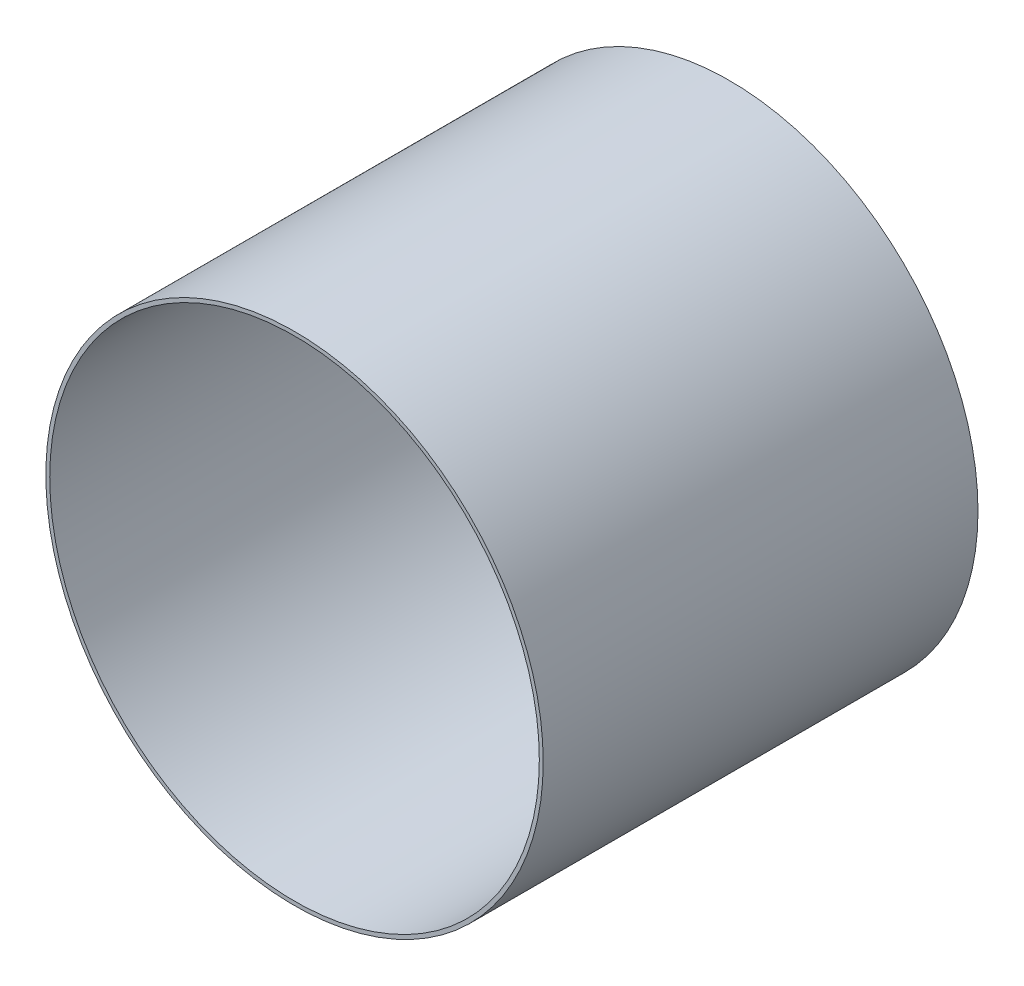
SolidWorks part; units mm, degrees
material "Titanio"
ref_plane "Piano frontale" through (0, 0, 0) normal (0, 0, 1) x (1, 0, 0)
ref_plane "Piano superiore" through (0, 0, 0) normal (0, 1, 0) x (1, 0, 0)
ref_plane "Piano destro" through (0, 0, 0) normal (1, 0, 0) x (0, 0, -1)
sketch "Schizzo1" plane through (0, 0, 0) normal (0, 0, 1) x (1, 0, 0)
  circle A0 centre (0, 0) radius 446.9
  circle A1 centre (0, 0) radius 439.9
  dimension "D1" = 893.8
  dimension "D2" = 7
extrude "Estrusione-Estrusione1" add sketch "Schizzo1" along normal blind 781.3
